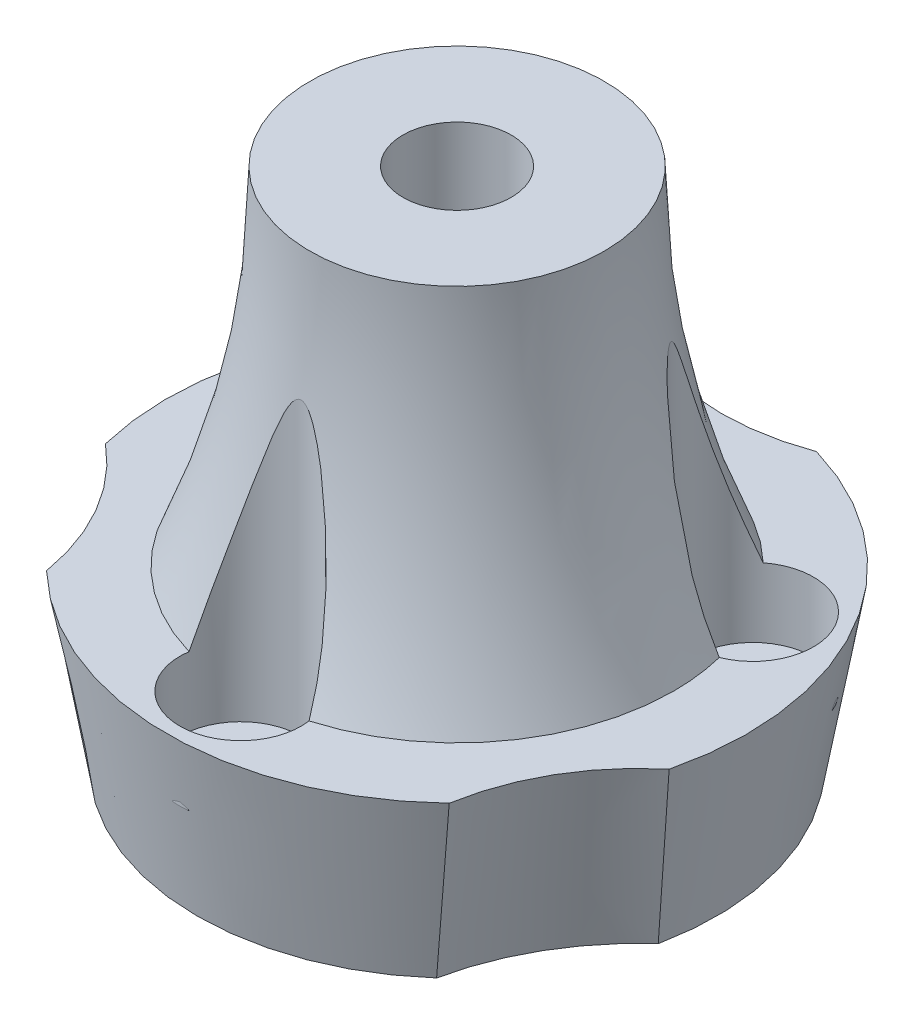
SolidWorks part; units mm, degrees
ref_plane "Front Plane" through (0, 0, 0) normal (0, 0, 1) x (1, 0, 0)
ref_plane "Top Plane" through (0, 0, 0) normal (0, 1, 0) x (1, 0, 0)
ref_plane "Right Plane" through (0, 0, 0) normal (1, 0, 0) x (0, 0, -1)
sketch "Sketch1" plane through (0, 0, 0) normal (0, 1, 0) x (1, 0, 0)
  line L0 (-8.051, 6.858) -> (9.6761, 6.858) construction
  line L1 (0, -12.8344) -> (0, 4.2232) construction
  line L2 (0, 0) -> (0, 14.478) construction
  line L3 (0, 0) -> (12.5383, -7.239) construction
  arc A0 (7.4588, -1.5589) -> (2.3793, 7.239) centre (0, 0) ccw
  arc A1 (-2.3793, 7.239) -> (2.3793, 7.239) centre (0, 14.478) ccw
  arc A2 (7.4588, -1.5589) -> (5.0795, -5.6801) centre (12.5383, -7.239) ccw
  arc A3 (-5.0795, -5.6801) -> (-7.4588, -1.5589) centre (-12.5383, -7.239) ccw
  arc A4 (-5.0795, -5.6801) -> (5.0795, -5.6801) centre (0, 0) ccw
  arc A5 (-2.3793, 7.239) -> (-7.4588, -1.5589) centre (0, 0) ccw
  dimension "D1" = 15.24
  dimension "D3" = 15.24
  dimension "D6" = 25.0766
  dimension "D7" = 14.478
  dimension "D2" = 6.858
  dimension "D4" = 3
  dimension "D5" = 120
extrude "Boss-Extrude1" add sketch "Sketch1" along normal blind 5.08 draft 10 draft outward yes
sketch "Sketch2" plane through (0, 5.08, 0) normal (0, 1, 0) x (1, 0, 0)
  line L0 (0, 0) -> (0, -15.3129) construction
  line L1 (0, 0.0555) -> (-1.3897, 0.0555) construction
  circle A0 centre (0, -6.35) radius 1.016
  arc A1 (-5.9052, -6.1357) -> (5.9052, -6.1357) centre (0, 0) ccw construction
  circle A2 centre (-5.4993, 3.175) radius 1.016
  circle A3 centre (5.4993, 3.175) radius 1.016
  arc A4 (8.2662, -2.0462) -> (2.3611, 8.1819) centre (0, 0) ccw construction
  point P14 (0, 0)
  dimension "D1" = 2.032
  dimension "D2" = 6.35
  dimension "D5" = 5.4993
  dimension "D3" = 3
  dimension "D4" = 10.9985
  dimension "D6" = 3.1195
  dimension "D7" = 6.35
extrude "Cut-Extrude1" cut sketch "Sketch2" against normal through all
sketch "Sketch3" plane through (0, 5.08, 0) normal (0, 1, 0) x (1, 0, 0)
  circle A0 centre (0, -6.35) radius 1.778
  circle A1 centre (-5.4993, 3.175) radius 1.778
  circle A2 centre (5.4993, 3.175) radius 1.778
  arc A3 (8.2662, -2.0462) -> (2.3611, 8.1819) centre (0, 0) ccw construction
  point P10 (0, 0)
  dimension "D1" = 3.556
  dimension "D4" = 6.35
  dimension "D3" = 6.35
  dimension "D2" = 3
extrude "Cut-Extrude2" cut sketch "Sketch3" against normal blind 2.032
sketch "Sketch4" plane through (0, 0, 0) normal (0, -1, 0) x (1, 0, 0)
  circle A0 centre (0, 0) radius 4.3815
  dimension "D1" = 8.763
extrude "Cut-Extrude3" cut sketch "Sketch4" against normal blind 2.032
sketch "Sketch5" plane through (0, 5.08, 0) normal (0, 1, 0) x (1, 0, 0)
  circle A0 centre (0, 0) radius 6.35 construction
  arc A1 (-2.3611, 8.1819) -> (-8.2662, -2.0462) centre (0, 0) ccw construction
  dimension "D1" = 12.7
  dimension "D2" = 0
sketch "Sketch6" plane through (0, 0, 0) normal (0, 0, 1) x (1, 0, 0)
  line L0 (0, 5.08) -> (0, 15.24)
  line L1 (0, 15.24) -> (4.318, 15.24)
  line L2 (6.35, 5.08) -> (-6.35, 5.08) construction
  line L3 (0, 5.08) -> (6.35, 5.08)
  arc A0 (4.318, 15.24) -> (6.35, 5.08) centre (30.734, 15.24) ccw
  dimension "D1" = 10.16
  dimension "D3" = 26.416
  dimension "D2" = 4.318
revolve "Revolve1" add sketch "Sketch6" angle 360 about L0
extrude "Cut-Extrude4" cut sketch "Sketch3<2>" against normal blind 2.032 and the other way blind 10.16
sketch "Sketch3<2>" plane through (0, 5.08, 0) normal (0, 1, 0) x (1, 0, 0) same geometry as "Sketch3"
sketch "Sketch7" plane through (0, 15.24, 0) normal (0, 1, 0) x (1, 0, 0)
  circle A0 centre (0, 0) radius 1.5875
  circle A1 centre (0, 0) radius 4.318 construction
  point P0 (0, 0)
  dimension "D1" = 3.175
  dimension "D2" = 2.7305
extrude "Cut-Extrude5" cut sketch "Sketch7" against normal blind 11.43
sketch "Sketch8" plane through (0, 0, 0) normal (0, 0, 1) x (1, 0, 0)
  line L1 (0, 0) -> (0, 5.9507) construction
  circle A0 centre (0, 12.7) radius 0.5
  dimension "D1" = 1
  dimension "D2" = 12.7
extrude "Cut-Extrude6" cut sketch "Sketch8" against normal through all
